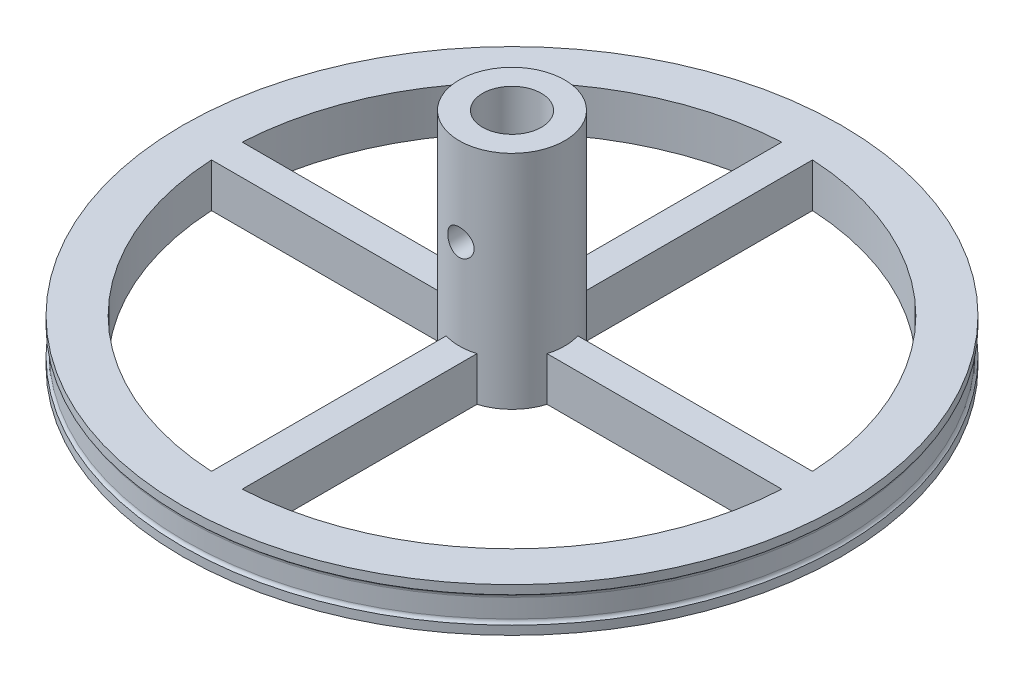
SolidWorks part; units mm, degrees
ref_plane "Front Plane" through (0, 0, 0) normal (0, 0, 1) x (1, 0, 0)
ref_plane "Top Plane" through (0, 0, 0) normal (0, 1, 0) x (1, 0, 0)
ref_plane "Right Plane" through (0, 0, 0) normal (1, 0, 0) x (0, 0, -1)
sketch "Sketch1" plane through (0, 0, 0) normal (0, 0, 1) x (1, 0, 0)
  line L0 (0, 2.2639) -> (0, -2.7361)
  line L1 (0, -2.7361) -> (37.5, -2.7361)
  line L2 (37.5, -2.7361) -> (37.5, -1.7361)
  line L3 (37.5, -1.7361) -> (37.25, -1.7361)
  line L4 (37.25, -1.7361) -> (37.25, 1.2639)
  line L5 (37.25, 1.2639) -> (37.5, 1.2639)
  line L6 (37.5, 1.2639) -> (37.5, 2.2639)
  line L7 (37.5, 2.2639) -> (0, 2.2639)
  dimension "D1" = 3
  dimension "D2" = 1
  dimension "D3" = 1
  dimension "D4" = 37.5
  dimension "D5" = 37.25
  dimension "D6" = 0.25
revolve "Revolve1" add sketch "Sketch1" angle 90 about L0
sketch "Sketch2" plane through (0, 0, 0) normal (0, 1, 0) x (1, 0, 0)
  line L0 (0, -37.5) -> (0, 0) construction
  line L1 (37.5, 0) -> (0, 0) construction
  line L2 (0, 0) -> (6, 0)
  line L3 (0, 0) -> (0, -6)
  arc A0 (0, -6) -> (6, 0) centre (0, 0) ccw
  dimension "D1" = 6
extrude "Boss-Extrude2" add sketch "Sketch2" along normal blind 22.5
sketch "Sketch6" plane through (0, 2.2639, 0) normal (0, 1, 0) x (1, 0, 0)
  line L0 (0, -37.5) -> (0, -6) construction
  line L1 (37.5, 0) -> (6, 0) construction
  line L2 (1.75, -5.7391) -> (1.75, -32.4529)
  line L3 (5.7391, -1.75) -> (32.4529, -1.75)
  arc A0 (1.75, -5.7391) -> (5.7391, -1.75) centre (0, 0) ccw
  arc A1 (1.75, -32.4529) -> (32.4529, -1.75) centre (0, 0) ccw
  dimension "D1" = 6
  dimension "D2" = 32.5
  dimension "D3" = 1.75
  dimension "D4" = 1.75
extrude "Cut-Extrude1" cut sketch "Sketch6" against normal through all
mirror "Mirror3" about plane through (0, 0, 0) normal (0, 0, 1) of "Cut-Extrude1", "Boss-Extrude2", "Revolve1"
mirror "Mirror4" about plane through (0, 0, 0) normal (1, 0, 0) of "Cut-Extrude1", "Mirror3", "Boss-Extrude2", "Revolve1"
sketch "Sketch7" plane through (0, 22.5, 0) normal (0, 1, 0) x (1, 0, 0)
  line L0 (0, 5.643) -> (0, -5.8158) construction
  line L1 (-6.3281, 0) -> (5.497, 0) construction
  circle A0 centre (0, 0) radius 3.35
  dimension "D1" = 6.7
extrude "Cut-Extrude2" cut sketch "Sketch7" against normal blind 20
fillet "Fillet9" radius 0.5 2 edges at (-37.25, -1.7361, 0) (-37.25, 1.2639, 0)
sketch "Sketch8" plane through (0, 0, 0) normal (0, 0, 1) x (1, 0, 0)
  line L0 (0, 22.5) -> (0, 0.2722) construction
  line L1 (3.35, 22.5) -> (-3.35, 22.5) construction
  line L2 (6, 22.5) -> (-6, 22.5) construction
  circle A0 centre (0, 12.5) radius 1.5
  dimension "D1" = 3
  dimension "D2" = 10
extrude "Cut-Extrude3" cut sketch "Sketch8" against normal up to next and the other way up to next
